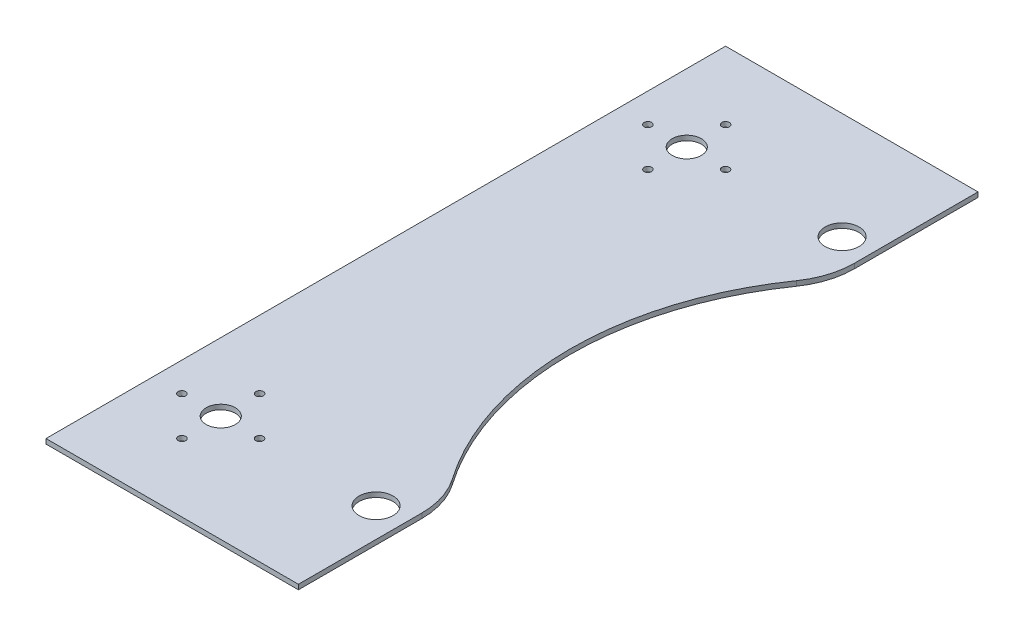
SolidWorks part; units mm, degrees
material "6061-T6 (SS)"
ref_plane "Front Plane" through (0, 0, 0) normal (0, 0, 1) x (1, 0, 0)
ref_plane "Top Plane" through (0, 0, 0) normal (0, 1, 0) x (1, 0, 0)
ref_plane "Right Plane" through (0, 0, 0) normal (1, 0, 0) x (0, 0, -1)
sketch "Sketch1" plane through (0, 0, 0) normal (0, 1, 0) x (1, 0, 0)
  line L1 (82.55, -222.25) -> (-82.55, -222.25)
  line L2 (82.55, -222.25) -> (82.55, 222.25)
  line L3 (82.55, 222.25) -> (-82.55, 222.25)
  line L4 (-82.55, -222.25) -> (-82.55, 222.25)
  line L5 (82.55, -222.25) -> (-82.55, 222.25) construction
  line L6 (82.55, 222.25) -> (-82.55, -222.25) construction
  point P0 (0, 0)
  dimension "D1" = 165.1
  dimension "D2" = 444.5
extrude "Boss-Extrude1" add sketch "Sketch1" along normal blind 3.175
sketch "Sketch3" plane through (0, 3.175, 0) normal (0, 1, 0) x (1, 0, 0)
  arc A0 (-28.575, -152.4) -> (-47.625, -152.4) centre (-38.1, -152.4) ccw construction
  arc A1 (-47.625, -152.4) -> (-28.575, -152.4) centre (-38.1, -152.4) ccw construction
  arc A2 (-28.575, -152.4) -> (-47.625, -152.4) centre (-38.1, -152.4) ccw
  arc A3 (-47.625, -152.4) -> (-28.575, -152.4) centre (-38.1, -152.4) ccw
  arc A4 (-28.575, 152.4) -> (-47.625, 152.4) centre (-38.1, 152.4) ccw construction
  arc A5 (-47.625, 152.4) -> (-28.575, 152.4) centre (-38.1, 152.4) ccw construction
  arc A6 (-28.575, 152.4) -> (-47.625, 152.4) centre (-38.1, 152.4) ccw
  arc A7 (-47.625, 152.4) -> (-28.575, 152.4) centre (-38.1, 152.4) ccw
extrude "Cut-Extrude2" cut sketch "Sketch3" against normal through all
hole_wizard "#10 (0.1935) Diameter Hole1" positions "Sketch4" profile "Sketch5" hole size "#10" standard "ANSI Inch" end condition through all
sketch "Sketch4" plane through (0, 3.175, 0) normal (0, 1, 0) x (1, 0, 0)
  arc A0 (-36.0807, -127) -> (-40.1193, -127) centre (-38.1, -127) ccw construction
  arc A1 (-40.1193, -127) -> (-36.0807, -127) centre (-38.1, -127) ccw construction
  arc A2 (-61.4807, -152.4) -> (-65.5193, -152.4) centre (-63.5, -152.4) ccw construction
  arc A3 (-65.5193, -152.4) -> (-61.4807, -152.4) centre (-63.5, -152.4) ccw construction
  arc A4 (-36.0807, -177.8) -> (-40.1193, -177.8) centre (-38.1, -177.8) ccw construction
  arc A5 (-40.1193, -177.8) -> (-36.0807, -177.8) centre (-38.1, -177.8) ccw construction
  arc A6 (-10.6807, -152.4) -> (-14.7193, -152.4) centre (-12.7, -152.4) ccw construction
  arc A7 (-14.7193, -152.4) -> (-10.6807, -152.4) centre (-12.7, -152.4) ccw construction
  arc A8 (-36.0807, -127) -> (-40.1193, -127) centre (-38.1, -127) ccw construction
  arc A9 (-40.1193, -127) -> (-36.0807, -127) centre (-38.1, -127) ccw construction
  arc A10 (-61.4807, -152.4) -> (-65.5193, -152.4) centre (-63.5, -152.4) ccw construction
  arc A11 (-65.5193, -152.4) -> (-61.4807, -152.4) centre (-63.5, -152.4) ccw construction
  arc A12 (-36.0807, -177.8) -> (-40.1193, -177.8) centre (-38.1, -177.8) ccw construction
  arc A13 (-40.1193, -177.8) -> (-36.0807, -177.8) centre (-38.1, -177.8) ccw construction
  arc A14 (-10.6807, -152.4) -> (-14.7193, -152.4) centre (-12.7, -152.4) ccw construction
  arc A15 (-14.7193, -152.4) -> (-10.6807, -152.4) centre (-12.7, -152.4) ccw construction
  arc A16 (-10.6807, 152.4) -> (-14.7193, 152.4) centre (-12.7, 152.4) ccw construction
  arc A17 (-14.7193, 152.4) -> (-10.6807, 152.4) centre (-12.7, 152.4) ccw construction
  arc A18 (-36.0807, 177.8) -> (-40.1193, 177.8) centre (-38.1, 177.8) ccw construction
  arc A19 (-40.1193, 177.8) -> (-36.0807, 177.8) centre (-38.1, 177.8) ccw construction
  arc A20 (-61.4807, 152.4) -> (-65.5193, 152.4) centre (-63.5, 152.4) ccw construction
  arc A21 (-65.5193, 152.4) -> (-61.4807, 152.4) centre (-63.5, 152.4) ccw construction
  arc A22 (-36.0807, 127) -> (-40.1193, 127) centre (-38.1, 127) ccw construction
  arc A23 (-40.1193, 127) -> (-36.0807, 127) centre (-38.1, 127) ccw construction
  arc A24 (-10.6807, 152.4) -> (-14.7193, 152.4) centre (-12.7, 152.4) ccw
  arc A25 (-14.7193, 152.4) -> (-10.6807, 152.4) centre (-12.7, 152.4) ccw
  arc A26 (-36.0807, 177.8) -> (-40.1193, 177.8) centre (-38.1, 177.8) ccw
  arc A27 (-40.1193, 177.8) -> (-36.0807, 177.8) centre (-38.1, 177.8) ccw
  arc A28 (-61.4807, 152.4) -> (-65.5193, 152.4) centre (-63.5, 152.4) ccw
  arc A29 (-65.5193, 152.4) -> (-61.4807, 152.4) centre (-63.5, 152.4) ccw
  arc A30 (-36.0807, 127) -> (-40.1193, 127) centre (-38.1, 127) ccw
  arc A31 (-40.1193, 127) -> (-36.0807, 127) centre (-38.1, 127) ccw
  point P0 (-38.1, -177.8)
  point P2 (-63.5, -152.4)
  point P4 (-38.1, -127)
  point P6 (-12.7, -152.4)
  point P44 (-38.1, 177.8)
  point P50 (-63.5, 152.4)
  point P56 (-38.1, 127)
  point P68 (-12.7, 152.4)
sketch "Sketch5" plane through (-38.1, 3.175, 177.8) normal (1, 0, 0) x (0, 0, 1)
  line L0 (0, 0) -> (0, 3.175)
  line L1 (0, 3.175) -> (2.4574, 3.175)
  line L2 (2.4574, 3.175) -> (2.4574, 0)
  line L5 (2.4574, 0) -> (0, 0)
  line L11 (0, -6.35) -> (0, 107.95) construction
  dimension "Thru Hole Dia." = 4.9149
  dimension "Thru Hole Depth" = 3.175
sketch "Sketch6" plane through (0, 3.175, 0) normal (0, 1, 0) x (1, 0, 0)
  line L0 (-38.1, -114.3) -> (-38.1, 114.3) construction
  line L1 (63.5, -152.4) -> (-38.1, -152.4) construction
  line L2 (63.5, 152.4) -> (-38.1, 152.4) construction
  line L3 (63.5, 152.4) -> (82.55, 152.4) construction
  line L4 (82.55, -222.25) -> (82.55, 222.25) construction
  circle A0 centre (-38.1, -152.4) radius 38.1 construction
  circle A1 centre (-38.1, 152.4) radius 38.1 construction
  circle A2 centre (63.5, -152.4) radius 38.1 construction
  circle A3 centre (63.5, 152.4) radius 38.1 construction
  dimension "D1" = 76.2
  dimension "D2" = 228.6
  dimension "D3" = 101.6
  dimension "D4" = 19.05
sketch "Sketch7" plane through (0, 3.175, 0) normal (0, 1, 0) x (1, 0, 0)
  circle A0 centre (63.5, -152.4) radius 11.1125
  circle A1 centre (63.5, 152.4) radius 11.1125
  dimension "D1" = 22.225
extrude "Cut-Extrude3" cut sketch "Sketch7" against normal through all
sketch "Sketch8" plane through (0, 3.175, 0) normal (0, 1, 0) x (1, 0, 0)
  line L0 (82.55, 222.25) -> (82.55, 141.5637)
  line L1 (82.55, -222.25) -> (82.55, 222.25) construction
  line L2 (82.55, -141.5637) -> (82.55, -222.25)
  line L3 (82.55, -222.25) -> (95.25, -222.25)
  line L4 (95.25, -222.25) -> (95.25, 222.25)
  line L5 (95.25, 222.25) -> (82.55, 222.25)
  arc A0 (82.55, 141.5637) -> (73.4321, 112.525) centre (31.75, 141.5637) cw
  arc A1 (73.4321, 112.525) -> (73.4321, -112.525) centre (234.95, 0) ccw
  arc A2 (73.4321, -112.525) -> (82.55, -141.5637) centre (31.75, -141.5637) cw
  dimension "D2" = 50.8
  dimension "D3" = 196.85
  dimension "D4" = 152.4
  dimension "D1" = 12.7
extrude "Cut-Extrude4" cut sketch "Sketch8" against normal through all
